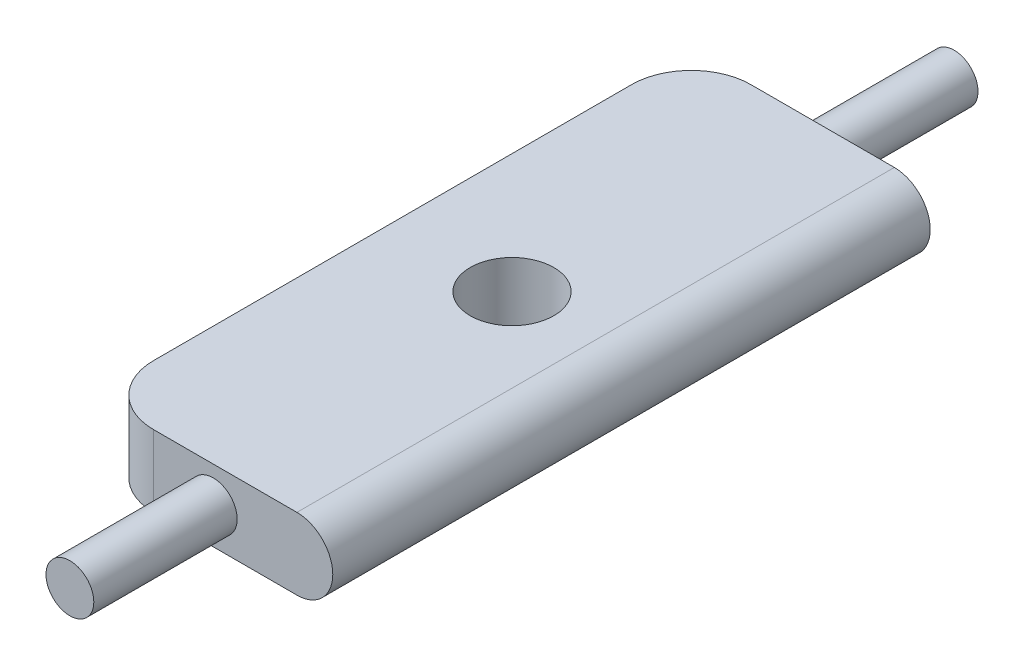
SolidWorks part; units mm, degrees
material "Plain Carbon Steel"
ref_plane "Front Plane" through (0, 0, 0) normal (0, 0, 1) x (1, 0, 0)
ref_plane "Top Plane" through (0, 0, 0) normal (0, 1, 0) x (1, 0, 0)
ref_plane "Right Plane" through (0, 0, 0) normal (1, 0, 0) x (0, 0, -1)
sketch "Sketch1" plane through (0, 0, 0) normal (0, 1, 0) x (1, 0, 0)
  line L1 (0, 0) -> (20, 0)
  line L2 (0, 0) -> (0, 50)
  line L3 (0, 50) -> (20, 50)
  line L4 (20, 0) -> (20, 50)
extrude "Boss-Extrude1" add sketch "Sketch1" along normal blind 6
sketch "Sketch2" plane through (0, 6, 0) normal (0, 1, 0) x (1, 0, 0)
  line L0 (10, 50) -> (10, 0)
  line L1 (20, 50) -> (0, 50) construction
  line L2 (0, 0) -> (20, 0) construction
  circle A0 centre (10, 25) radius 3.5
extrude "Cut-Extrude1" cut sketch "Sketch2" against normal through all contours L0 A0 | L0 A0 region at (11.4854, 6, -25) region at (8.5146, 6, -25)
sketch "Sketch3" plane through (0, 0, 0) normal (0, 0, 1) x (1, 0, 0)
  line L0 (10, 6) -> (10, 0)
  line L1 (0, 6) -> (20, 6) construction
  line L2 (0, 0) -> (20, 0) construction
  circle A0 centre (10, 3) radius 2
extrude "Boss-Extrude2" add sketch "Sketch3" along normal blind 4 contours L0 A0 | L0 A0 region at (10.8488, 3, 0) region at (9.1512, 3, 0)
sketch "Sketch4" plane through (0, 0, -50) normal (0, 0, -1) x (-1, 0, 0)
  line L0 (-10, 6) -> (-10, 0)
  line L1 (-20, 6) -> (0, 6) construction
  line L2 (-20, 0) -> (0, 0) construction
  circle A0 centre (-10, 3) radius 2
extrude "Boss-Extrude3" add sketch "Sketch4" along normal blind 4 contours L0 A0 | L0 A0 region at (9.1512, 3, -50) region at (10.8488, 3, -50)
sketch "Sketch5" plane through (0, 0, -54) normal (0, 0, -1) x (-1, 0, 0)
  circle A1 centre (-10, 3) radius 2
  circle A2 centre (-10, 3) radius 2
  dimension "D1" = 0
extrude "Boss-Extrude4" add sketch "Sketch5" along normal blind 1
sketch "Sketch6" plane through (0, 0, 4) normal (0, 0, 1) x (1, 0, 0)
  circle A1 centre (10, 3) radius 2
  circle A2 centre (10, 3) radius 2
  dimension "D1" = 0
extrude "Boss-Extrude5" add sketch "Sketch6" along normal blind 1
fillet "Fillet1" radius 5 1 edges at (0, 3, -50) type face fillet first side face at (12, 3, -50) second side face at (0, 3, -25)
fillet "Fillet2" radius 5 1 edges at (0, 3, 0) type face fillet first side face at (8, 3, 0) second side face at (0, 3, -22.5)
fillet "Fillet3" 2 edges at (20, 6, -25) (20, 0, -25) type full round first side face at (10, 6, -21.5) second side face at (10, 0, -21.5) middle face at (20, 3, -25)
sketch "Sketch7" plane through (0, 0, -55) normal (0, 0, -1) x (-1, 0, 0)
  circle A1 centre (-10, 3) radius 2
  circle A2 centre (-10, 3) radius 2
  dimension "D1" = 0
extrude "Boss-Extrude6" add sketch "Sketch7" along normal blind 7
sketch "Sketch8" plane through (0, 0, 5) normal (0, 0, 1) x (1, 0, 0)
  circle A1 centre (10, 3) radius 2
  circle A2 centre (10, 3) radius 2
  dimension "D1" = 0
extrude "Boss-Extrude7" add sketch "Sketch8" along normal blind 7
